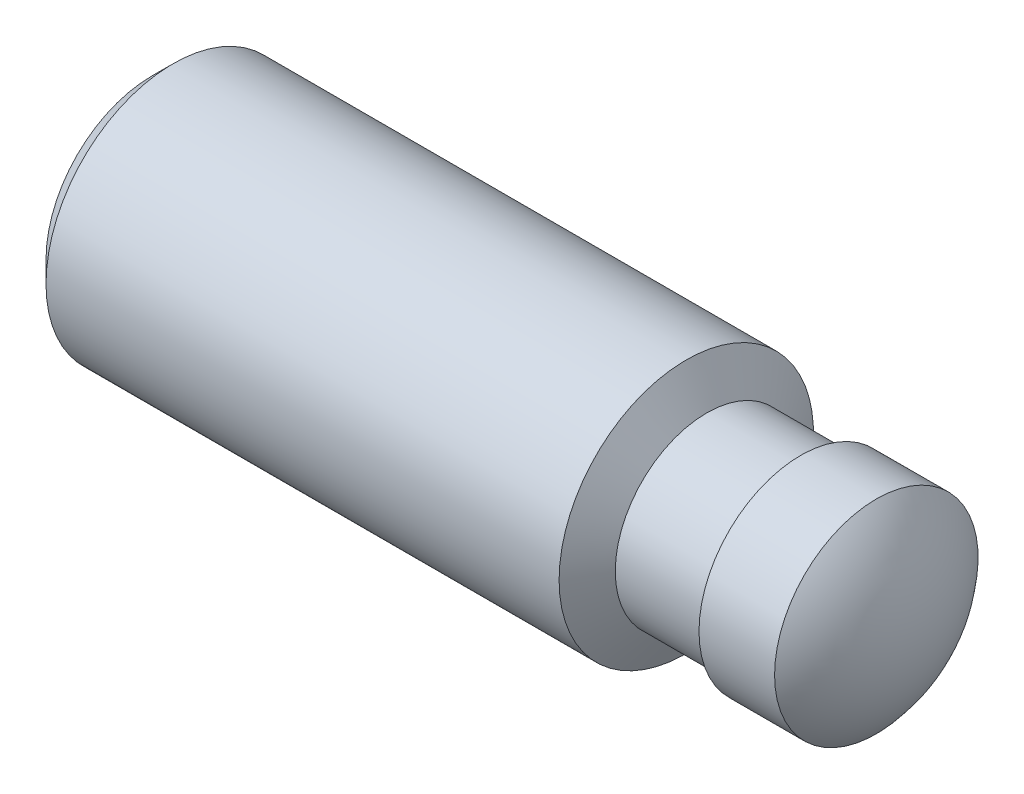
SolidWorks part; units mm, degrees
revolve "BaseBody" add sketch "BodySke" angle 360 about L5 other way angle 60
sketch "BodySke" plane through (0, 0, 0) normal (0, 0, 1) x (1, 0, 0)
  line L0 (0.828, -5) -> (19.05, -5) construction
  line L1 (21.8083, 3.6) -> (25.5, 3.6)
  line L2 (0.828, 5) -> (21, 5)
  line L3 (21.8083, 3.6) -> (21, 5)
  line L5 (-3.175, 0) -> (33.7104, 0) construction
  line L6 (1.5, 12.7) -> (1.5, -6.35) construction
  line L7 (25.5, 3.6) -> (25.5, 4)
  line L8 (21.8083, -3.6) -> (25.5, -3.6) construction
  line L9 (0, 0) -> (0, 4.172)
  line L10 (0, 4.172) -> (0.828, 5)
  line L11 (25.5, 4) -> (28.4721, 4)
  line L12 (30, 0) -> (0, 0)
  arc A0 (28.4721, 4) -> (30, 0) centre (24, 0) cw
  dimension "Diameter" = 10
  dimension "Drive_ch_ang" = 45
  dimension "D1" = 60
  dimension "Dog_dia" = 8
  dimension "Length" = 30
cosmetic thread "ThreadCosmetic" [suppressed] parameters "Thread_minor"=8.344
ref_plane "Plane1" through (0, 0, 0) normal (0, 0, 1) x (1, 0, 0)
ref_plane "Plane2" through (0, 0, 0) normal (0, 1, 0) x (1, 0, 0)
ref_plane "Plane3" through (0, 0, 0) normal (1, 0, 0) x (0, 0, -1)
sketch "ThdSchSke" plane through (0, 0, 0) normal (0, 0, 1) x (1, 0, 0)
  line L0 (0.828, -4.172) -> (0.2482, -5)
  line L1 (0.828, -4.172) -> (1.4078, -5)
  line L2 (1.4078, -5) -> (1.4078, -6.25)
  line L3 (-3.175, 0) -> (5.1513, 0) construction
  line L5 (1.4078, -6.25) -> (0.2482, -6.25)
  line L6 (0.2482, -6.25) -> (0.2482, -5)
  line L7 (0.828, -5) -> (0.828, 5) construction
  dimension "Diameter" = 10
  dimension "Thread_minor" = 8.344
revolve "ThreadSchematic" [suppressed] cut sketch "ThdSchSke" angle 360 about L3
pattern_linear "ThdSchPat" [suppressed]
equation "\"Thread_minor@ThreadCosmetic\" = \"Minor_dia@BodySke\""
equation "\"Thread_minor@ThdSchSke\" = \"Thread_minor@ThreadCosmetic\""
equation "\"Diameter@ThdSchSke\" = \"Diameter@BodySke\""
equation "\"Overcut@ThdSchSke\" = \"Diameter@BodySke\" * 1.25"
equation "\"Num_threads@ThdSchPat\" = int( (\"Length@BodySke\" - ( ( ( \"Diameter@BodySke\" - \"Minor_dia@BodySke\" ) * 0.5 ) / tan( \"Drive_ch_ang@BodySke\" * 0.017453292 ) ) - \"pt_len@BodySke\" ) / \"Advance@BodySke\" + 0.999 )  + 1"
equation "\"Advance@ThdSchPat\" = (\"Length@BodySke\" - ( ( ( \"Diameter@BodySke\" - \"Minor_dia@BodySke\" ) * 0.5 ) / tan( \"Drive_ch_ang@BodySke\" * 0.017453292 ) ) - \"pt_len@BodySke\" ) /  (\"Num_threads@ThdSchPat\" - 1) 'relax it"
equation "'  \"Num_threads@ThdSchPat\" = \"Num_threads@ThdSchPat\" - sgn( \"Num_threads@ThdSchPat\" - 1) '---chamfered tips only---"
